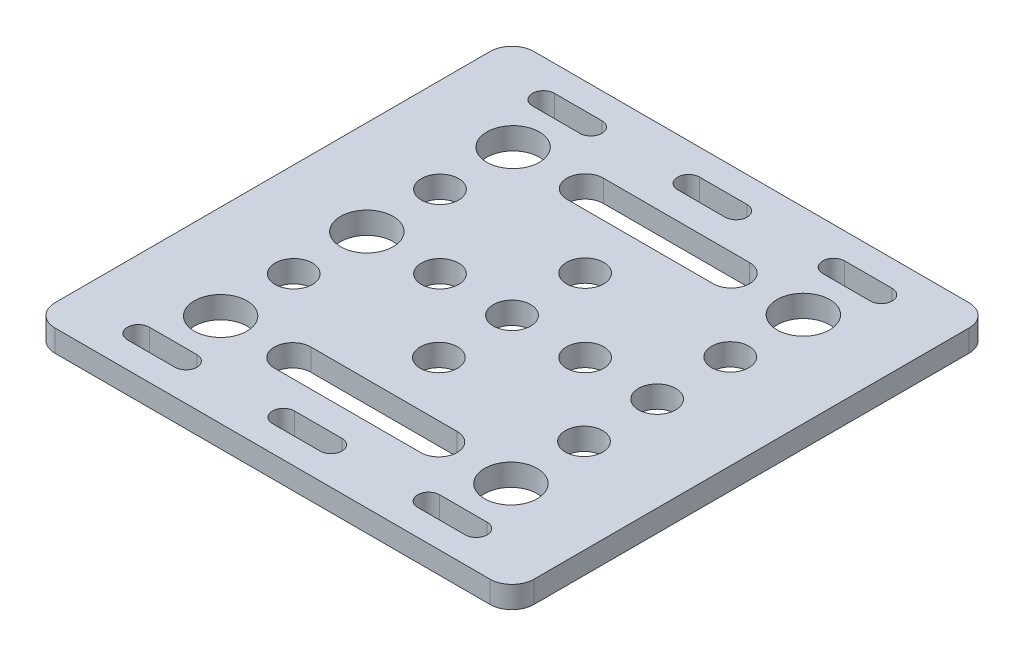
SolidWorks part; units mm, degrees
ref_plane "Płaszczyzna przednia" through (0, 0, 0) normal (0, 0, 1) x (1, 0, 0)
ref_plane "Płaszczyzna górna" through (0, 0, 0) normal (0, 1, 0) x (1, 0, 0)
ref_plane "Płaszczyzna prawa" through (0, 0, 0) normal (1, 0, 0) x (0, 0, -1)
sketch "Szkic1" plane through (0, 0, 0) normal (0, 1, 0) x (1, 0, 0)
  line L0 (9.35, 60.45) -> (15.85, 60.45) construction
  line L1 (3, 0) -> (62.5, 0)
  line L2 (0, 3) -> (0, 62.5)
  line L3 (3, 65.5) -> (62.5, 65.5)
  line L4 (65.5, 3) -> (65.5, 62.5)
  line L5 (9.35, 61.95) -> (15.85, 61.95)
  line L6 (9.35, 58.95) -> (15.85, 58.95)
  line L7 (29.2, 58.95) -> (35.7, 58.95)
  line L8 (29.2, 61.95) -> (35.7, 61.95)
  line L9 (29.2, 60.45) -> (35.7, 60.45) construction
  line L10 (49.05, 58.95) -> (55.55, 58.95)
  line L11 (49.05, 61.95) -> (55.55, 61.95)
  line L12 (49.05, 60.45) -> (55.55, 60.45) construction
  line L13 (29.2, 3.55) -> (35.7, 3.55)
  line L14 (29.2, 6.55) -> (35.7, 6.55)
  line L15 (29.2, 5.05) -> (35.7, 5.05) construction
  line L16 (49.05, 3.55) -> (55.55, 3.55)
  line L17 (49.05, 6.55) -> (55.55, 6.55)
  line L18 (49.05, 5.05) -> (55.55, 5.05) construction
  line L19 (9.35, 3.55) -> (15.85, 3.55)
  line L20 (9.35, 6.55) -> (15.85, 6.55)
  line L21 (9.35, 5.05) -> (15.85, 5.05) construction
  line L22 (22.75, 12.75) -> (42.75, 12.75) construction
  line L23 (22.75, 15.25) -> (42.75, 15.25)
  line L24 (22.75, 10.25) -> (42.75, 10.25)
  line L25 (22.75, 50.25) -> (42.75, 50.25)
  line L26 (22.75, 55.25) -> (42.75, 55.25)
  line L27 (22.75, 52.75) -> (42.75, 52.75) construction
  arc A0 (9.35, 61.95) -> (9.35, 58.95) centre (9.35, 60.45) ccw
  arc A1 (15.85, 58.95) -> (15.85, 61.95) centre (15.85, 60.45) ccw
  arc A2 (29.2, 61.95) -> (29.2, 58.95) centre (29.2, 60.45) ccw
  arc A3 (35.7, 58.95) -> (35.7, 61.95) centre (35.7, 60.45) ccw
  arc A4 (49.05, 61.95) -> (49.05, 58.95) centre (49.05, 60.45) ccw
  arc A5 (55.55, 58.95) -> (55.55, 61.95) centre (55.55, 60.45) ccw
  arc A6 (29.2, 6.55) -> (29.2, 3.55) centre (29.2, 5.05) ccw
  arc A7 (35.7, 3.55) -> (35.7, 6.55) centre (35.7, 5.05) ccw
  arc A8 (49.05, 6.55) -> (49.05, 3.55) centre (49.05, 5.05) ccw
  arc A9 (55.55, 3.55) -> (55.55, 6.55) centre (55.55, 5.05) ccw
  arc A10 (9.35, 6.55) -> (9.35, 3.55) centre (9.35, 5.05) ccw
  arc A11 (15.85, 3.55) -> (15.85, 6.55) centre (15.85, 5.05) ccw
  circle A16 centre (12.9, 32.75) radius 3.6
  circle A19 centre (12.9, 42.75) radius 2.55
  circle A20 centre (32.75, 42.75) radius 2.55
  circle A21 centre (52.6, 42.75) radius 2.55
  circle A22 centre (32.75, 32.75) radius 2.55
  circle A23 centre (52.6, 32.75) radius 2.55
  circle A24 centre (32.75, 22.75) radius 2.55
  circle A25 centre (52.6, 22.75) radius 2.55
  circle A27 centre (12.9, 22.75) radius 2.55
  circle A28 centre (12.9, 32.75) radius 2.55 [skipped]
  circle A29 centre (42.75, 32.75) radius 2.55
  circle A30 centre (42.75, 32.75) radius 2.55
  circle A31 centre (22.9, 32.75) radius 2.55
  arc A32 (0, 62.5) -> (3, 65.5) centre (3, 62.5) cw
  arc A33 (62.5, 65.5) -> (65.5, 62.5) centre (62.5, 62.5) cw
  arc A34 (62.5, 0) -> (65.5, 3) centre (62.5, 3) ccw
  arc A35 (3, 0) -> (0, 3) centre (3, 3) cw
  arc A36 (22.75, 15.25) -> (22.75, 10.25) centre (22.75, 12.75) ccw
  arc A37 (42.75, 10.25) -> (42.75, 15.25) centre (42.75, 12.75) ccw
  arc A38 (22.75, 55.25) -> (22.75, 50.25) centre (22.75, 52.75) ccw
  arc A39 (42.75, 50.25) -> (42.75, 55.25) centre (42.75, 52.75) ccw
  point P7 (12.6, 60.45)
  point P17 (32.45, 60.45)
  point P24 (52.3, 60.45)
  point P31 (32.45, 5.05)
  point P38 (52.3, 5.05)
  point P45 (12.6, 5.05)
  point P87 (65.5, 65.5)
  point P90 (65.5, 0)
  point P93 (0, 0)
  point P96 (32.75, 12.75)
  point P104 (32.75, 52.75)
  dimension "D14" = 5.1
  dimension "D15" = 12.9
  dimension "D16" = 22.75
  dimension "D21" = 3
  dimension "D1" = 65.5
  dimension "D2" = 65.5
  dimension "D3" = 9.35
  dimension "D4" = 6.5
  dimension "D5" = 5.05
  dimension "D6" = 3
  dimension "D22" = 5
  dimension "D23" = 32.75
  dimension "D24" = 20
  dimension "D25" = 52.75
  dimension "D7" = 3
  dimension "D8" = 2
  dimension "D17" = 3
  dimension "D18" = 3
  dimension "D19" = 2
  dimension "D20" = 2
  dimension "D26" = 2
extrude "Dodanie-wyciągnięcie1" add sketch "Szkic1" along normal blind 3 contours A35 L1 A34 L4 A33 L3 A32 L2 A39 L25 A38 L26 A37 L24 A36 L23 A31 A29 A27 A25 A24 A23 A22 A21 A20 A19 A16 A11 L19 region at (1.5337, 0, -1.5337)
hole_wizard "Otwory ustalające Ø10.0mm1" positions "Szkic2" profile "Szkic3" hole size "Ø10.0" standard "Ansi Metric"
sketch "Szkic2" plane through (0, 3, 0) normal (0, 1, 0) x (1, 0, 0)
  point P0 (12.9, 12.75)
  point P3 (12.9, 52.75)
  point P6 (52.6, 12.75)
  point P9 (52.6, 52.75)
sketch "Szkic3" plane through (12.9, 3, -12.75) normal (1, 0, 0) x (0, 0, 1)
  line L0 (0, 0) -> (0, 13.6631)
  line L1 (0, 13.6631) -> (3.6, 11.5)
  line L2 (3.6, 11.5) -> (3.6, 0)
  line L5 (3.6, 0) -> (0, 0)
  line L10 (0, 13.6631) -> (-3.6, 11.5) construction
  line L11 (0, -6.35) -> (0, 107.95) construction
  dimension "Œrednica otworu" = 7.2
  dimension "G³êbokoœæ otworu" = 11.5
  dimension "K¹t wiert³a" = 118
